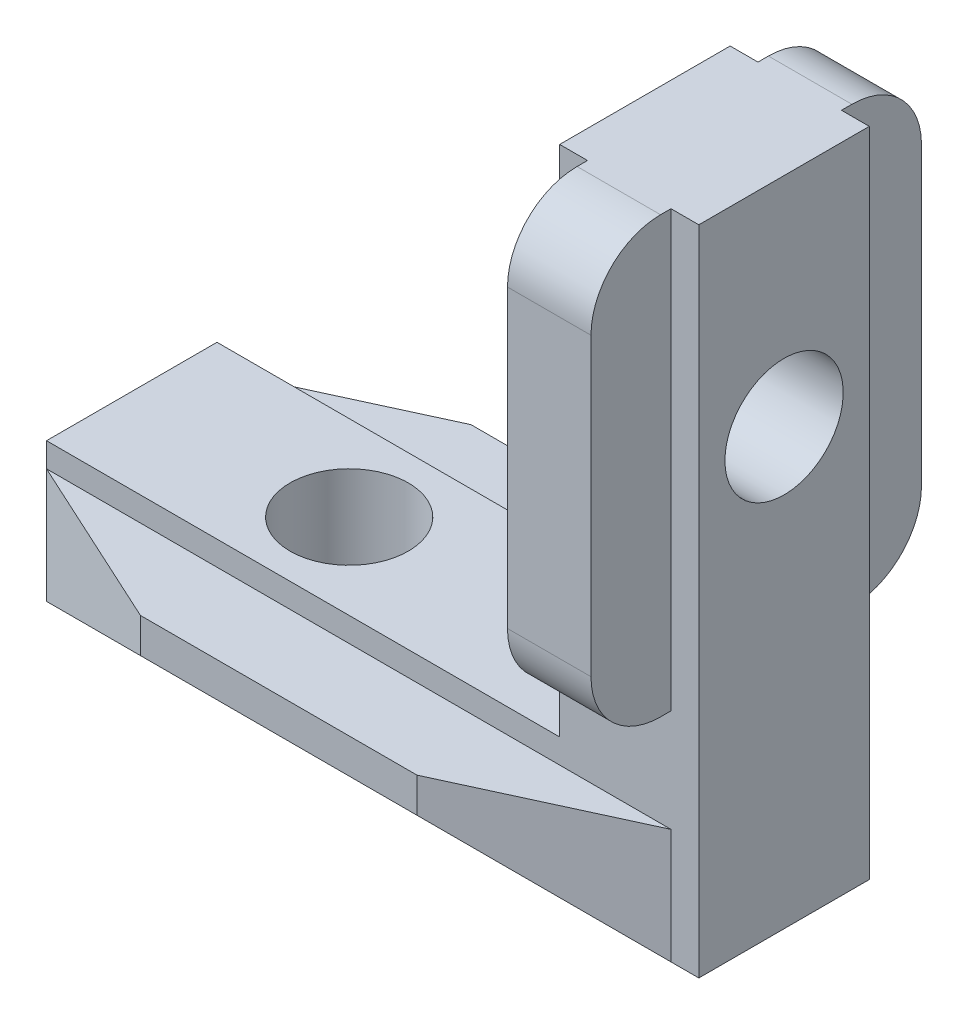
SolidWorks part; units mm, degrees
ref_plane "前视基准面" through (0, 0, 0) normal (0, 0, 1) x (1, 0, 0)
ref_plane "上视基准面" through (0, 0, 0) normal (0, 1, 0) x (1, 0, 0)
ref_plane "右视基准面" through (0, 0, 0) normal (1, 0, 0) x (0, 0, -1)
sketch "草图1" plane through (0, 0, 0) normal (0, 0, 1) x (1, 0, 0)
  line B0 (-37.5, 0) -> (0, 0)
  line B1 (0, 0) -> (0, 37.5)
  line B2 (-37.5, 8) -> (-8, 8)
  line B3 (-8, 8) -> (-8, 37.5)
  line B4 (-37.5, 8) -> (-37.5, 0)
  line B5 (-8, 37.5) -> (0, 37.5)
sketch_block_instance "A$C70755ADE-1"
sketch_block "A$C70755ADE"
extrude "凸台-拉伸1" add sketch "草图1" along normal mid plane 9.8
sketch "草图3" plane through (-37.5, 0, 0) normal (-1, 0, 0) x (0, 0, 1)
  line L0 (-4.9, 0) -> (-9.5, 4.6)
  line L1 (-9.5, 4.6) -> (-9.5, 6.6)
  line L2 (-9.5, 6.6) -> (-4.9, 6.6)
  line L3 (-4.9, 8) -> (-4.9, 0) construction
  line L4 (-4.9, 6.6) -> (-4.9, 0)
  line L5 (4.9, 8) -> (-4.9, 8) construction
  line L6 (-4.9, 37.5) -> (-4.9, 8) construction
  line L7 (0, 0) -> (0, 10.3417) construction
  line L8 (4.9, 6.6) -> (4.9, 0)
  line L9 (9.5, 6.6) -> (4.9, 6.6)
  line L10 (9.5, 4.6) -> (9.5, 6.6)
  line L11 (4.9, 0) -> (9.5, 4.6)
  dimension "D1" = 1.4
  dimension "D2" = 4.6
  dimension "D3" = 45
extrude "凸台-拉伸2" add sketch "草图3" against normal blind 35.9
chamfer "倒角1" distance 10 distance2 4.6 2 edges at (-37.5, 5.6, 9.5) (-37.5, 5.6, -9.5) first distance on face at (-19.55, 5.6, 9.5) first distance on face at (-19.55, 5.6, -9.5)
chamfer "倒角2" distance 4.6 distance2 10 2 edges at (-1.6, 5.6, 9.5) (-1.6, 5.6, -9.5) first distance on face at (-1.6, 4.7, 6.625) first distance on face at (-1.6, 4.2, -7.775)
ref_plane "基准面2" through (-4, 0, 0) normal (-1, 0, 0) x (0, 0, 1)
sketch "草图5" plane through (-4, 0, 0) normal (-1, 0, 0) x (0, 0, 1)
  line L0 (-4.9, 37.5) -> (-5.5, 37.5)
  line L1 (-9.5, 33.5) -> (-9.5, 16.5)
  line L2 (-5.5, 12.5) -> (-4.9, 12.5)
  line L3 (-4.9, 37.5) -> (-4.9, 8) construction
  line L4 (-4.9, 12.5) -> (-4.9, 37.5)
  line L5 (-9.5, 4.6) -> (-9.5, 6.6) construction
  line L6 (0, 37.5) -> (0, 22.0148) construction
  line L7 (4.9, 37.5) -> (-4.9, 37.5) construction
  line L8 (9.5, 6.6) -> (9.5, 4.6) construction
  line L9 (4.9, 12.5) -> (4.9, 37.5)
  line L10 (5.5, 12.5) -> (4.9, 12.5)
  line L11 (9.5, 33.5) -> (9.5, 16.5)
  line L12 (4.9, 37.5) -> (5.5, 37.5)
  arc A0 (-9.5, 16.5) -> (-5.5, 12.5) centre (-5.5, 16.5) ccw
  arc A1 (-5.5, 37.5) -> (-9.5, 33.5) centre (-5.5, 33.5) ccw
  arc A2 (5.5, 37.5) -> (9.5, 33.5) centre (5.5, 33.5) cw
  arc A3 (9.5, 16.5) -> (5.5, 12.5) centre (5.5, 16.5) cw
  point P11 (-9.5, 12.5)
  point P14 (-9.5, 37.5)
  point P29 (9.5, 37.5)
  point P30 (9.5, 12.5)
  dimension "D2" = 4
  dimension "D3" = 4
  dimension "D1" = 25
extrude "凸台-拉伸3" add sketch "草图5" along normal mid plane 4.8
sketch "草图6" plane through (0, 8, 0) normal (0, 1, 0) x (1, 0, 0)
  line L0 (0, -4.9) -> (0, 4.9) construction
  point P0 (-25, 0)
  dimension "D1" = 25
hole_wizard "M8 螺纹孔1" positions "3D草图1" profile "草图7" tap size "M8" standard "Iso"
sketch3d "3D草图1"
  point P0 (-25, 8, 0)
sketch "草图7" plane through (-25, 8, 0) normal (1, 0, 0) x (0, 0, 1)
  line L0 (0, 0) -> (0, 21.7929)
  line L1 (0, 21.7929) -> (3.4, 19.75)
  line L2 (3.4, 19.75) -> (3.4, 0)
  line L5 (3.4, 0) -> (0, 0)
  line L10 (0, 21.7929) -> (-3.4, 19.75) construction
  line L11 (0, -6.35) -> (0, 107.95) construction
  dimension "螺纹孔钻头直径" = 6.8
  dimension "螺纹孔钻头深度" = 19.75
  dimension "导头角度" = 118
cosmetic thread "孔螺蚊线1"
ref_plane "基准面3" through (0, 0, 0) normal (-0.7071, -0.7071, 0) x (-0.7071, 0.7071, 0)
mirror "镜向1" about plane through (0, 0, 0) normal (-0.7071, -0.7071, 0) of "M8 螺纹孔1"
